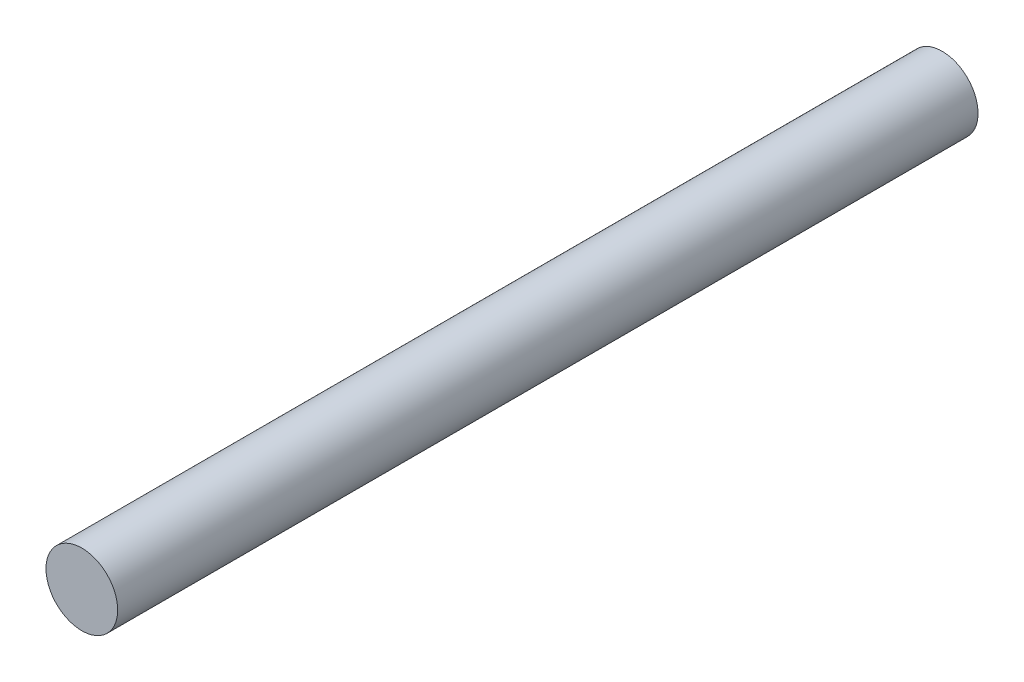
SolidWorks part; units mm, degrees
ref_plane "Front Plane" through (0, 0, 0) normal (0, 0, 1) x (1, 0, 0)
ref_plane "Top Plane" through (0, 0, 0) normal (0, 1, 0) x (1, 0, 0)
ref_plane "Right Plane" through (0, 0, 0) normal (1, 0, 0) x (0, 0, -1)
sketch "Sketch1" plane through (0, 0, 0) normal (0, 0, 1) x (1, 0, 0)
  circle A0 centre (0, 0) radius 6.35
extrude "Boss-Extrude1" add sketch "Sketch1" along normal blind 152.4
